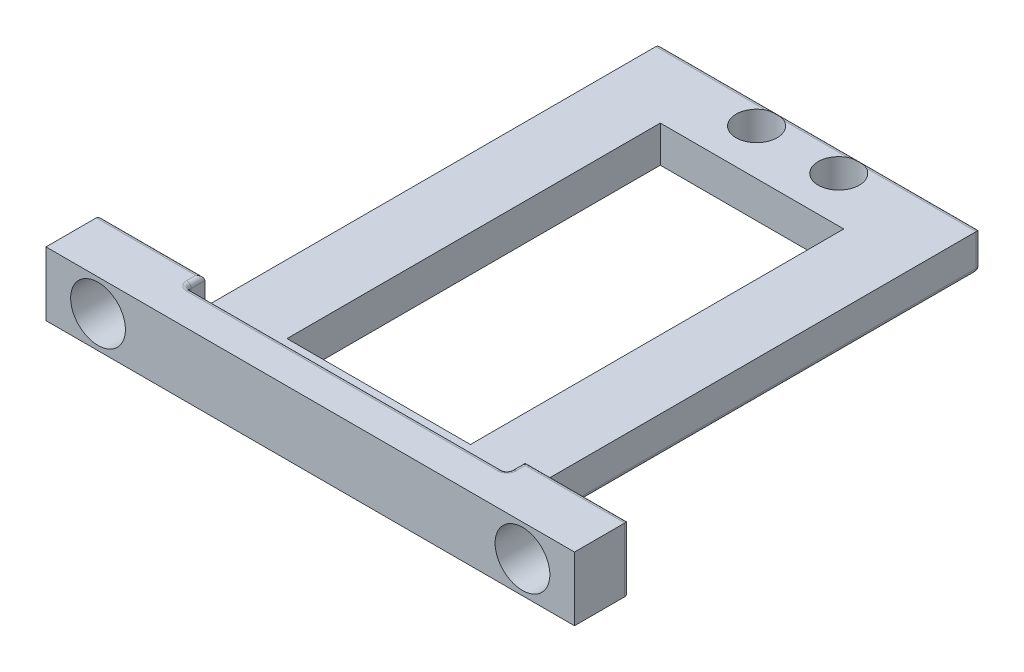
SolidWorks part; units mm, degrees
material "Alliage 1060"
ref_plane "Plan de dessus" through (0, 0, 0) normal (0, 0, 1) x (1, 0, 0)
ref_plane "Plan de droite" through (0, 0, 0) normal (0, 1, 0) x (1, 0, 0)
ref_plane "Plan de face" through (0, 0, 0) normal (1, 0, 0) x (0, 0, -1)
sketch "Esquisse1" plane through (0, 0, 0) normal (0, 1, 0) x (1, 0, 0)
  line L13 (3.6, -21) -> (3.6, 19.9)
  line L14 (-16.5, -21) -> (3.6, -21)
  line L15 (3.6, 19.9) -> (-16.5, 19.9)
  line L20 (-16.5, 19.9) -> (-16.5, -21)
  line L21 (-24, 27.4) -> (11.1, 27.4)
  line L26 (11.1, -28.5) -> (-24, -28.5)
  line L27 (11.1, -28.5) -> (11.1, 27.4)
  line L29 (-24, -28.5) -> (-24, 27.4)
  dimension "D1" = 35.1
  dimension "D2" = 7.5
  dimension "D3" = 7.5
  dimension "D4" = 7.5
  dimension "D5" = 7.5
  dimension "D6" = 40.9
extrude "Boss.-Extru.1" add sketch "Esquisse1" along normal blind 4 contours L29 L21 L27 L26 | L20 L14 L13 L15
sketch "Esquisse5" plane through (0, 0, 28.5) normal (0, 0, 1) x (1, 0, 0)
  line L29 (11.1, 7) -> (11.1, 4)
  line L30 (-6.45, 4) -> (-6.45, 7)
  line L31 (11.1, 4) -> (-24, 4) construction
  line L32 (-6.45, 7) -> (11.1, 7)
  line L33 (-6.45, 4) -> (11.1, 4)
  line L34 (-6.45, 7) -> (-6.45, 20.1757) construction
extrude "Boss.-Extru.2" add sketch "Esquisse5" against normal blind 4
ref_plane "Plan2" through (-6.45, 0, 0) normal (1, 0, 0) x (0, 0, -1)
mirror "Symétrie1" about plane through (-6.45, 0, 0) normal (1, 0, 0) of "Boss.-Extru.2"
sketch "Esquisse7" plane through (0, 0, 28.5) normal (0, 0, 1) x (1, 0, 0)
  line L0 (22.5, 7) -> (22.5, 0)
  line L1 (11.1, 7) -> (22.5, 7)
  line L2 (11.1, 0) -> (11.1, 7)
  line L3 (11.1, 0) -> (22.5, 0)
  line L4 (-24, 7) -> (-24, 0) construction
  line L5 (11.1, 7) -> (-24, 7) construction
  dimension "D1" = 11.4
  dimension "D2" = 7
  dimension "D3" = 35.1
extrude "Boss.-Extru.3" add sketch "Esquisse7" against normal blind 6
sketch "Esquisse8" plane through (0, 0, 22.5) normal (0, 0, -1) x (-1, 0, 0)
  line L0 (-22.5, 3.5) -> (-11.1, 3.5) construction
  line L1 (-22.5, 0) -> (-22.5, 7) construction
  line L2 (-11.1, 4) -> (-11.1, 0) construction
  circle A2 centre (-16.8, 3.5) radius 3
  dimension "D2" = 6
extrude "Enlèv. mat.-Extru.1" cut sketch "Esquisse8" against normal blind 6
mirror "Symétrie2" about plane through (-6.45, 0, 0) normal (1, 0, 0) of "Boss.-Extru.3"
mirror "Symétrie3" about plane through (-6.45, 0, 0) normal (1, 0, 0) of "Enlèv. mat.-Extru.1"
fillet "Congé1" radius 0.5 16 edges at (11.1, 7, 23.5) (-24, 7, 23.5) (-24, 0, -2.45) (11.1, 0, -2.45) (11.1, 5.5, 24.5) (-6.45, 7, 24.5) (-24, 5.5, 24.5) (-6.45, 4, 24.5) (-29.7, 7, 22.5) (-35.4, 3.5, 22.5) (-29.7, 0, 22.5) (-24, 2, 22.5) (11.1, 2, 22.5) (16.8, 0, 22.5) (22.5, 3.5, 22.5) (16.8, 7, 22.5)
fillet "Congé2" radius 0.5 6 edges at (10.9536, 0.1464, -27.4) (11.1, 2.25, -27.4) (-6.45, 4, -27.4) (-24, 2.25, -27.4) (-23.8536, 0.1464, -27.4) (-6.45, 0, -27.4)
sketch "Esquisse9" plane through (0, 0, 0) normal (0, -1, 0) x (1, 0, 0)
  line L0 (10.6, -24.9) -> (-1.95, -24.9) construction
  line L2 (-1.95, -24.9) -> (-10.95, -24.9) construction
  line L3 (-23.5, 22) -> (-23.5, -26.9) construction
  line L4 (10.6, -26.9) -> (10.6, 22) construction
  line L5 (-23.5, -24.9) -> (-10.95, -24.9) construction
  line L6 (22.5, 23) -> (22.5, 28.5) construction
  line L7 (22.5, 28.5) -> (-35.4, 28.5) construction
  circle A0 centre (-1.95, -24.9) radius 2.25
  circle A1 centre (-10.95, -24.9) radius 2.25
  dimension "D1" = 4.5
  dimension "D2" = 24.45
  dimension "D3" = 53.4
extrude "Enlèv. mat.-Extru.2" cut sketch "Esquisse9" against normal up to next
